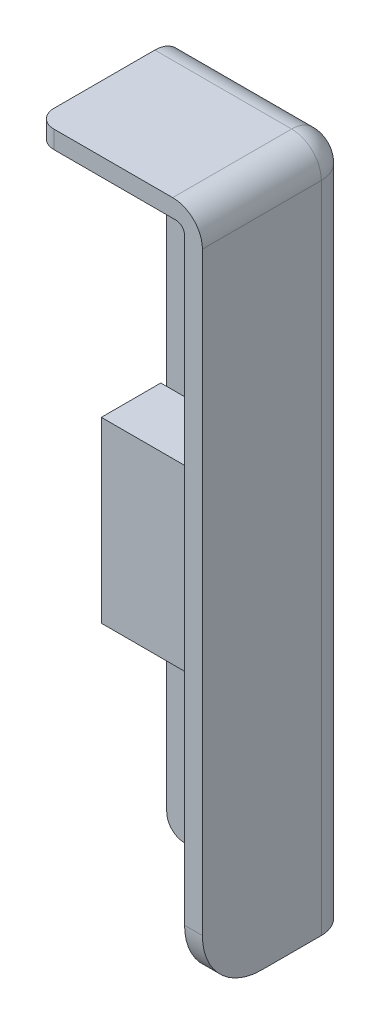
SolidWorks part; units mm, degrees
material "ABS"
ref_plane "Front" through (0, 0, 0) normal (0, 0, 1) x (1, 0, 0)
ref_plane "Top" through (0, 0, 0) normal (0, 1, 0) x (1, 0, 0)
ref_plane "Right" through (0, 0, 0) normal (1, 0, 0) x (0, 0, -1)
sketch "Sketch1" plane through (0, 0, 0) normal (1, 0, 0) x (0, 0, -1)
  line L1 (-12.5, 57.5) -> (12.5, 57.5)
  line L2 (-12.5, 57.5) -> (-12.5, -57.5)
  line L3 (-12.5, -57.5) -> (12.5, -57.5)
  line L4 (12.5, 57.5) -> (12.5, -57.5)
  line L5 (-12.5, 57.5) -> (12.5, -57.5) construction
  line L6 (-12.5, -57.5) -> (12.5, 57.5) construction
  point P0 (0, 0)
  dimension "D1" = 25
  dimension "D2" = 115
extrude "Boss-Extrude1" add sketch "Sketch1" along normal mid plane 28
sketch "Sketch3" plane through (-14, 0, 0) normal (1, 0, 0) x (0, 0, -1)
  line L1 (-12.5, -57.5) -> (9.5, -57.5)
  line L2 (-12.5, -57.5) -> (-12.5, 54.5)
  line L3 (-12.5, 54.5) -> (9.5, 54.5)
  line L4 (9.5, -57.5) -> (9.5, 54.5)
  dimension "D1" = 22
  dimension "D2" = 112
extrude "Cut-Extrude1" cut sketch "Sketch3" along normal offset from surface (25 mm away) 3 up to face at (14, 0, 0)
sketch "Sketch4" plane through (11, 0, 0) normal (-1, 0, 0) x (0, 0, 1)
  line L0 (12.5, -1.5) -> (-9.5, -1.5) construction
  line L1 (12.5, 54.5) -> (12.5, -57.5) construction
  line L2 (-9.5, -57.5) -> (-9.5, 54.5) construction
  line L4 (-3.5, 13.5) -> (6.5, 13.5)
  line L5 (-3.5, 13.5) -> (-3.5, -16.5)
  line L6 (-3.5, -16.5) -> (6.5, -16.5)
  line L7 (6.5, 13.5) -> (6.5, -16.5)
  line L8 (-3.5, 13.5) -> (6.5, -16.5) construction
  line L9 (-3.5, -16.5) -> (6.5, 13.5) construction
  point P6 (1.5, -1.5)
  dimension "D1" = 30
  dimension "D2" = 10
extrude "Boss-Extrude2" add sketch "Sketch4" along normal blind 20
hole_wizard "#2 Clearance Hole1" positions "Sketch5" profile "Sketch6" hole size "#2" standard "ANSI Inch"
sketch "Sketch5" plane through (-9, 0, 0) normal (-1, 0, 0) x (0, 0, 1)
  line L0 (1.5, 13.5) -> (1.5, -16.5) construction
  line L1 (6.5, 13.5) -> (-3.5, 13.5) construction
  line L2 (-3.5, -16.5) -> (6.5, -16.5) construction
  line L4 (-3.5, -1.5) -> (6.5, -1.5) construction
  line L5 (-3.5, 13.5) -> (-3.5, -16.5) construction
  line L6 (6.5, -16.5) -> (6.5, 13.5) construction
  point P0 (1.5, 8.5)
  point P2 (1.5, -11.5)
  dimension "D1" = 10
  dimension "D2" = 10
sketch "Sketch6" plane through (-9, 8.5, 1.5) normal (0, 1, 0) x (0, 0, 1)
  line L0 (0, 0) -> (0, 7.0292)
  line L1 (0, 7.0292) -> (1.1303, 6.35)
  line L2 (1.1303, 6.35) -> (1.1303, 0)
  line L5 (1.1303, 0) -> (0, 0)
  line L10 (0, 7.0292) -> (-1.1303, 6.35) construction
  line L11 (0, -6.35) -> (0, 107.95) construction
  dimension "Hole Dia." = 2.2606
  dimension "Hole Depth" = 6.35
  dimension "Drill Angle" = 118
fillet "Fillet1" radius 1.5 3 edges at (11, -1.5, -9.5) (-1.5, 54.5, -9.5) (11, 54.5, 1.5)
fillet "Fillet3" radius 5 3 edges at (0, 57.5, -12.5) (14, 57.5, 0) (14, 0, -12.5)
fillet "Fillet4" radius 10 1 edges at (12.5, -57.5, 12.5)
fillet "Fillet5" radius 3 2 edges at (-14, -57.5, -11) (-14, 56, 12.5)
fillet "Fillet6" radius 3 4 edges at (11, 13.5, 1.5) (11, -1.5, -3.5) (11, -16.5, 1.5) (11, -1.5, 6.5)
sketch "Sketch7" plane through (14, 0, 0) normal (1, 0, 0) x (0, 0, -1)
  circle A0 centre (-1.5, -43) radius 3.875 construction
  arc A1 (-3.4751, -46.3339) -> (-4.0856, -40.1138) centre (-1.5, -43) ccw construction
  circle A2 centre (-1.5, -43) radius 2.875
  dimension "D1" = 1
extrude "Boss-Extrude3" add sketch "Sketch7" against normal blind 8
fillet "Fillet7" radius 1 2 edges at (11, -43, -1.375) (6, -43, -1.375)
move or copy body "Body-Move/Copy1" [suppressed] bodies to move or copy 105
